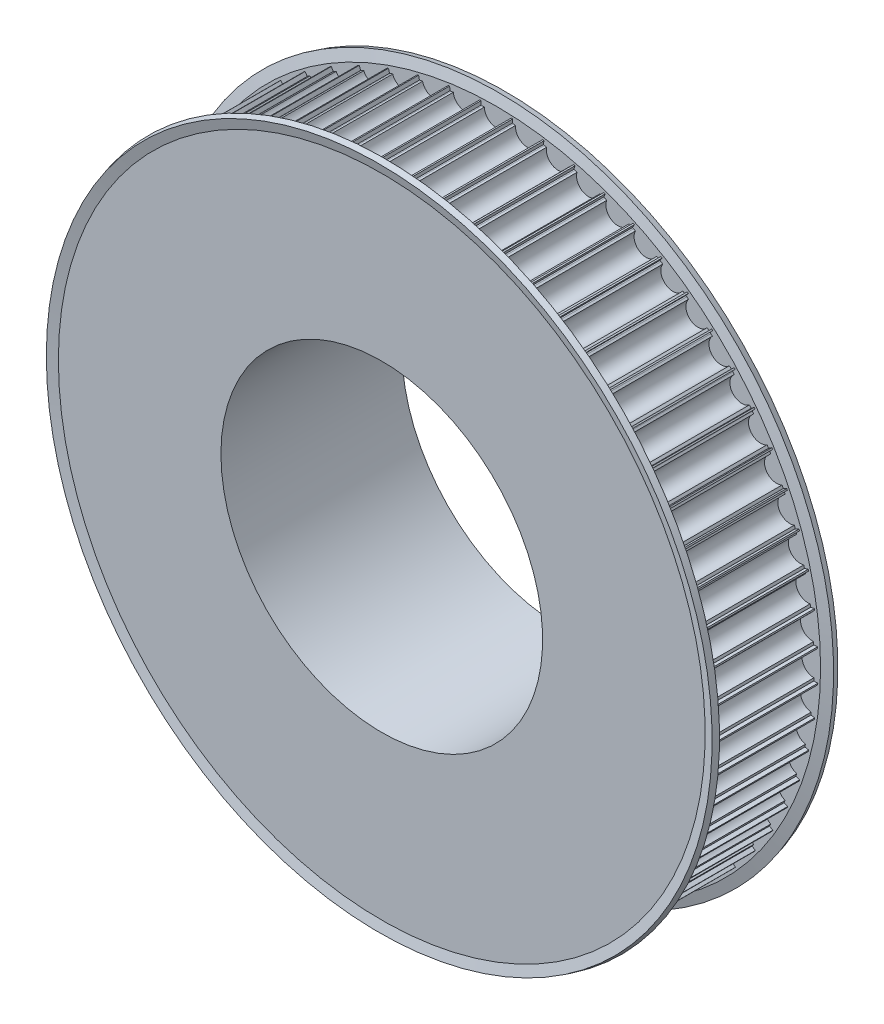
SolidWorks part; units mm, degrees
ref_plane "Front Plane" through (0, 0, 0) normal (0, 0, 1) x (1, 0, 0)
ref_plane "Top Plane" through (0, 0, 0) normal (0, 1, 0) x (1, 0, 0)
ref_plane "Right Plane" through (0, 0, 0) normal (1, 0, 0) x (0, 0, -1)
ref_axis "Axis1" through (0, 0, -88.99) along (0, 0, 1)
sketch "Sketch1" plane through (0, 0, 0) normal (1, 0, 0) x (0, 0, -1)
  line L0 (0, 40) -> (0, 80)
  line L1 (0, 80) -> (30, 80)
  line L2 (30, 80) -> (30, 55.5)
  line L3 (30, 55.5) -> (45, 55.5)
  line L4 (45, 55.5) -> (45, 40)
  line L5 (45, 40) -> (0, 40)
  line L6 (88.99, 0) -> (-88.99, 0) construction
  point P4 (0, 0)
  dimension "D1" = 40
  dimension "D2" = 15.5
  dimension "D3" = 15
  dimension "D4" = 30
  dimension "D5" = 40
revolve "Revolve1" add sketch "Sketch1" angle 360 about axis through (0, 0, -88.99) along (0, 0, 1)
sketch "Sketch3" plane through (0, 0, 0) normal (0, 0, 1) x (1, 0, 0)
  line L0 (0, -1000) -> (0, 76) construction
  line L1 (2.9995, 78.9449) -> (3.6864, 78.9449)
  line L2 (-3.8136, 81.5) -> (3.6864, 81.5)
  line L3 (-3.8136, 81.5) -> (-3.8136, 78.9449)
  line L4 (-3.8136, 78.9449) -> (-2.9995, 78.9449)
  line L5 (3.6864, 81.5) -> (3.6864, 78.9449)
  line L6 (0, 79) -> (0, 49000) construction
  arc A0 (-2.9995, 78.9449) -> (2.9995, 78.9449) centre (0, 79) ccw
  circle A1 centre (0, 0) radius 80 construction
  arc A2 (-3.8136, 78.9449) -> (-2.9326, 78.3677) centre (-3.6658, 78.2097) cw
  arc A3 (2.9301, 78.3563) -> (3.6864, 78.9449) centre (3.6626, 78.1953) cw
  point P12 (0, 80)
  circle M5 centre (0, 0) radius 80
  dimension "D1" = 3
  dimension "D5" = 0.75
  dimension "D2" = 79
  dimension "D3" = 7.5
  dimension "D4" = 1.5
extrude "Cut-Extrude1" cut sketch "Sketch3" against normal through all contours L1 A3 L5 L3 A2 L4 A0 M5 region at (-0.021, 78.3271, 0)
pattern_circular "CirPattern1" count 64 over 360 about axis through (0, 0, -88.99) along (0, 0, 1) of "Cut-Extrude1"
sketch "Sketch4" plane through (0, 0, 0) normal (1, 0, 0) x (0, 0, -1)
  line L1 (0, 80.615) -> (1.5, 80.615) construction
  line L2 (0, 80.615) -> (0, 75.615) construction
  line L3 (0, 75.615) -> (1.5, 75.615)
  line L4 (1.5, 80.615) -> (1.5, 75.615)
  line L5 (0.8155, 83.1695) -> (1.5, 80.615)
  line L6 (0.8155, 83.1695) -> (-0.6334, 82.7813)
  line L7 (1.5, 80.615) -> (0.0511, 80.2268) construction
  line L8 (-0.6334, 82.7813) -> (0.0511, 80.2268) construction
  line L9 (0, 79.8981) -> (0, 78.9386) construction
  line L10 (0, 75.615) -> (0, 80.4175)
  line L11 (0, 80.4175) -> (-0.6334, 82.7813)
  line L12 (15, 79.8981) -> (15, 87.0161) construction
  line L13 (30, 79.8981) -> (0, 79.8981) construction
  line L14 (29.1845, 83.1695) -> (30.6334, 82.7813)
  line L15 (30, 80.4175) -> (30.6334, 82.7813)
  line L16 (30, 75.615) -> (30, 80.4175)
  line L17 (30, 75.615) -> (28.5, 75.615)
  line L18 (28.5, 80.615) -> (28.5, 75.615)
  line L19 (29.1845, 83.1695) -> (28.5, 80.615)
revolve "Revolve2" add sketch "Sketch4" angle 360 about axis through (0, 0, -88.99) along (0, 0, 1)
